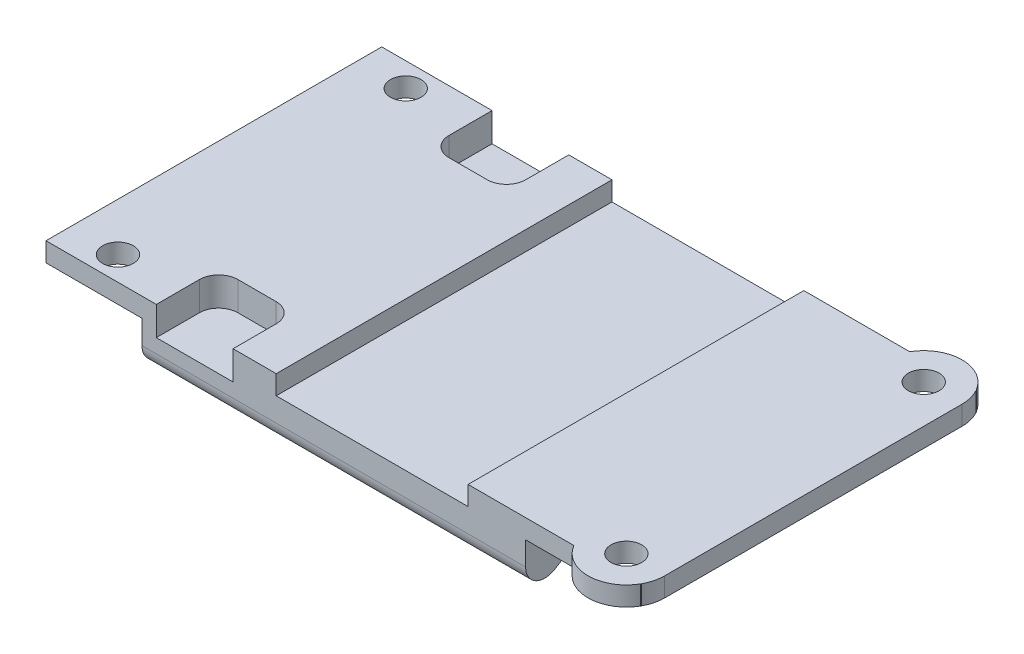
SolidWorks part; units mm, degrees
material "PEI"
ref_plane "Front Plane" through (0, 0, 0) normal (0, 0, 1) x (1, 0, 0)
ref_plane "Top Plane" through (0, 0, 0) normal (0, 1, 0) x (1, 0, 0)
ref_plane "Right Plane" through (0, 0, 0) normal (1, 0, 0) x (0, 0, -1)
sketch "Sketch1" plane through (0, 0, 0) normal (0, 1, 0) x (1, 0, 0)
  line L1 (20, -17.5) -> (-20, -17.5)
  line L2 (20, -17.5) -> (20, 17.5)
  line L3 (20, 17.5) -> (-20, 17.5)
  line L4 (-20, -17.5) -> (-20, 17.5)
  line L5 (20, -17.5) -> (-20, 17.5) construction
  line L6 (20, 17.5) -> (-20, -17.5) construction
  point P0 (0, 0)
  dimension "D1" = 35
  dimension "D2" = 40
extrude "Boss-Extrude1" add sketch "Sketch1" against normal blind 8
sketch "Sketch2" plane through (20, 0, 0) normal (1, 0, 0) x (0, 0, -1)
  line L0 (-17.5, -8) -> (-12.5, -5)
  line L1 (-12.5, -5) -> (12.5, -5)
  line L2 (0, -5) -> (0, -8)
  line L3 (17.5, -8) -> (12.5, -5)
  line L4 (17.5, 0) -> (-17.5, 0)
  line L5 (-17.5, 0) -> (-17.5, -8)
  line L6 (-17.5, -8) -> (17.5, -8)
  line L7 (17.5, -8) -> (17.5, 0)
  line L8 (17.5, 0) -> (-17.5, 0)
  line L9 (-17.5, 0) -> (-17.5, -8)
  line L10 (-17.5, -8) -> (17.5, -8)
  line L11 (17.5, -8) -> (17.5, 0)
  line M7 (-17.5, -8) -> (17.5, -8)
  dimension "D2" = 5
  dimension "D3" = 3
  dimension "D1" = 0
extrude "Cut-Extrude1" cut sketch "Sketch2" against normal through all and the other way through all contours L2 L1 L0 M7 | L3 L1 L2 M7 region at (20, -6.5833, 7.5694) region at (20, -6.5833, -7.5694)
fillet "Fillet1" radius 2 4 edges at (0, -5, 12.5) (0, -5, -12.5) (0, -8, -17.5) (0, -8, 17.5)
sketch "Sketch4" plane through (-20, 0, 0) normal (-1, 0, 0) x (0, 0, 1)
  line L1 (-17.5, 0) -> (17.5, 0)
  line L2 (-17.5, 0) -> (-17.5, -2)
  line L3 (-17.5, -2) -> (17.5, -2)
  line L4 (17.5, 0) -> (17.5, -2)
  line L6 (-17.5, 0) -> (-17.5, -4.4676)
  line L7 (-14.471, -6.1826) -> (-12.975, -5.285)
  line L8 (-11.946, -5) -> (11.946, -5)
  line L9 (12.975, -5.285) -> (14.471, -6.1826)
  line L10 (17.5, -4.4676) -> (17.5, 0)
  line L11 (17.5, 0) -> (-17.5, 0)
  line L12 (-17.5, 0) -> (-17.5, -4.4676)
  line L13 (-14.471, -6.1826) -> (-12.975, -5.285)
  line L14 (-11.946, -5) -> (11.946, -5)
  line L15 (12.975, -5.285) -> (14.471, -6.1826)
  line L16 (17.5, -4.4676) -> (17.5, 0)
  line L17 (17.5, 0) -> (-17.5, 0)
  arc A4 (-17.5, -4.4676) -> (-14.471, -6.1826) centre (-15.5, -4.4676) ccw
  arc A5 (-11.946, -5) -> (-12.975, -5.285) centre (-11.946, -7) ccw
  arc A6 (12.975, -5.285) -> (11.946, -5) centre (11.946, -7) ccw
  arc A7 (14.471, -6.1826) -> (17.5, -4.4676) centre (15.5, -4.4676) ccw
  arc A8 (-17.5, -4.4676) -> (-14.471, -6.1826) centre (-15.5, -4.4676) ccw
  arc A9 (-11.946, -5) -> (-12.975, -5.285) centre (-11.946, -7) ccw
  arc A10 (12.975, -5.285) -> (11.946, -5) centre (11.946, -7) ccw
  arc A11 (14.471, -6.1826) -> (17.5, -4.4676) centre (15.5, -4.4676) ccw
  line M12 (-17.5, 0) -> (-17.5, -4.4676)
  line M20 (17.5, -4.4676) -> (17.5, 0)
  line M21 (17.5, 0) -> (-17.5, 0)
  dimension "D2" = 2
  dimension "D1" = 0
extrude "Boss-Extrude2" add sketch "Sketch4" along normal blind 10 contours L3 M12 M20 M21 region at (-20, -1, 0)
sketch "Sketch5" plane through (20, 0, 0) normal (1, 0, 0) x (0, 0, -1)
  line L1 (-17.5, 0) -> (17.5, 0)
  line L2 (-17.5, 0) -> (-17.5, -2)
  line L3 (-17.5, -2) -> (17.5, -2)
  line L4 (17.5, 0) -> (17.5, -2)
  line L6 (12.975, -5.285) -> (14.471, -6.1826)
  line L7 (17.5, -4.4676) -> (17.5, 0)
  line L8 (17.5, 0) -> (-17.5, 0)
  line L9 (-17.5, 0) -> (-17.5, -4.4676)
  line L10 (-14.471, -6.1826) -> (-12.975, -5.285)
  line L11 (-11.946, -5) -> (11.946, -5)
  line L12 (12.975, -5.285) -> (14.471, -6.1826)
  line L13 (17.5, -4.4676) -> (17.5, 0)
  line L14 (17.5, 0) -> (-17.5, 0)
  line L15 (-17.5, 0) -> (-17.5, -4.4676)
  line L16 (-14.471, -6.1826) -> (-12.975, -5.285)
  line L17 (-11.946, -5) -> (11.946, -5)
  arc A4 (14.471, -6.1826) -> (17.5, -4.4676) centre (15.5, -4.4676) ccw
  arc A5 (-17.5, -4.4676) -> (-14.471, -6.1826) centre (-15.5, -4.4676) ccw
  arc A6 (-11.946, -5) -> (-12.975, -5.285) centre (-11.946, -7) ccw
  arc A7 (12.975, -5.285) -> (11.946, -5) centre (11.946, -7) ccw
  arc A8 (14.471, -6.1826) -> (17.5, -4.4676) centre (15.5, -4.4676) ccw
  arc A9 (-17.5, -4.4676) -> (-14.471, -6.1826) centre (-15.5, -4.4676) ccw
  arc A10 (-11.946, -5) -> (-12.975, -5.285) centre (-11.946, -7) ccw
  arc A11 (12.975, -5.285) -> (11.946, -5) centre (11.946, -7) ccw
  line M14 (17.5, -4.4676) -> (17.5, 0)
  line M15 (17.5, 0) -> (-17.5, 0)
  line M16 (-17.5, 0) -> (-17.5, -4.4676)
  dimension "D2" = 2
  dimension "D1" = 0
extrude "Boss-Extrude3" add sketch "Sketch5" along normal blind 12 contours L3 M16 M14 M15 region at (20, -1, 0)
sketch "Sketch6" plane through (0, -2, 0) normal (0, -1, 0) x (1, 0, 0)
  line L0 (0, 0) -> (-25, 0)
  line L1 (-25, 0) -> (-25, 15)
  line L4 (-20, -17.5) -> (-20, 17.5)
  line L5 (-20, 17.5) -> (-30, 17.5)
  line L6 (-30, 17.5) -> (-30, -17.5)
  line L7 (-30, -17.5) -> (-20, -17.5)
  line L8 (-20, -17.5) -> (-20, 17.5)
  line L9 (-20, 17.5) -> (-30, 17.5)
  line L10 (-30, 17.5) -> (-30, -17.5)
  line L11 (-30, -17.5) -> (-20, -17.5)
  line L12 (20, -11.946) -> (20, 11.946)
  line L13 (20, 11.946) -> (-20, 11.946)
  line L14 (-20, 11.946) -> (-20, -11.946)
  line L15 (-20, -11.946) -> (20, -11.946)
  line L16 (20, -11.946) -> (20, 11.946)
  line L17 (20, 11.946) -> (-20, 11.946)
  line L18 (-20, 11.946) -> (-20, -11.946)
  line L19 (-20, -11.946) -> (20, -11.946)
  circle A0 centre (-25, 15) radius 1.6
  circle A1 centre (-25, -15) radius 1.6
  dimension "D5" = 3.2
  dimension "D3" = 15
  dimension "D4" = 25
  dimension "D1" = 0
  dimension "D2" = 0
extrude "Cut-Extrude2" cut sketch "Sketch6" against normal blind 10 contours A1 | A0 region at (-26.0994, -2, 16.0994) region at (-25, -2, -15)
sketch "Sketch7" plane through (0, 0, 0) normal (0, 1, 0) x (1, 0, 0)
  line L0 (-25, -15) -> (-14.5, -15)
  line L1 (-14.5, -15) -> (-14.5, -14.5)
  line L2 (0, 0) -> (-16.7205, 0)
  line L3 (-10.5, -19) -> (-18.5, -19)
  line L4 (32, 17.5) -> (-30, 17.5)
  line L5 (-30, 17.5) -> (-30, -17.5)
  line L6 (-30, -17.5) -> (32, -17.5)
  line L7 (32, -17.5) -> (32, 17.5)
  line L8 (32, 17.5) -> (-30, 17.5)
  line L9 (-30, 17.5) -> (-30, -17.5)
  line L10 (-30, -17.5) -> (32, -17.5)
  line L11 (32, -17.5) -> (32, 17.5)
  line L12 (-10.5, -19) -> (-10.5, -11)
  line L13 (-10.5, -11) -> (-18.5, -11)
  line L14 (-18.5, -19) -> (-18.5, -11)
  line L15 (-10.5, -19) -> (-18.5, -11) construction
  line L16 (-10.5, -11) -> (-18.5, -19) construction
  line L17 (-10.5, 19) -> (-18.5, 19)
  line L18 (-18.5, 19) -> (-18.5, 11)
  line L19 (-10.5, 19) -> (-10.5, 11)
  line L20 (-10.5, 11) -> (-18.5, 11)
  dimension "D4" = 8
  dimension "D2" = 0.5
  dimension "D3" = 10.5
  dimension "D5" = 8
  dimension "D1" = 0
extrude "Cut-Extrude3" cut sketch "Sketch7" against normal blind 3 contours L20 L19 L8 L18 | L12 L13 L14 L3 region at (-14.5, 0, -14.25)
sketch "Sketch8" plane through (0, 0, 17.5) normal (0, 0, 1) x (1, 0, 0)
  line L0 (-10.5, 0) -> (32, 0) construction
  line L1 (14, 2) -> (-6, 2)
  line L2 (14, 2) -> (14, -2)
  line L3 (14, -2) -> (-6, -2)
  line L4 (-6, 2) -> (-6, -2)
  line L5 (14, 2) -> (-6, -2) construction
  line L6 (14, -2) -> (-6, 2) construction
  line L12 (-10.5, -3) -> (-18.5, -3)
  line L13 (-18.5, -3) -> (-18.5, 0)
  line L14 (-18.5, 0) -> (-30, 0)
  line L15 (-30, 0) -> (-30, -2)
  line L16 (-30, -2) -> (-20, -2)
  line L17 (-20, -2) -> (-20, -4.4676)
  line L18 (-20, -4.4676) -> (20, -4.4676)
  line L19 (20, -4.4676) -> (20, -2)
  line L20 (20, -2) -> (32, -2)
  line L21 (32, -2) -> (32, 0)
  line L22 (32, 0) -> (-10.5, 0)
  line L23 (-10.5, 0) -> (-10.5, -3)
  line L24 (-10.5, -3) -> (-18.5, -3)
  line L25 (-18.5, -3) -> (-18.5, 0)
  line L26 (-18.5, 0) -> (-30, 0)
  line L27 (-30, 0) -> (-30, -2)
  line L28 (-30, -2) -> (-20, -2)
  line L29 (-20, -2) -> (-20, -4.4676)
  line L30 (-20, -4.4676) -> (20, -4.4676)
  line L31 (20, -4.4676) -> (20, -2)
  line L32 (20, -2) -> (32, -2)
  line L33 (32, -2) -> (32, 0)
  line L34 (32, 0) -> (-10.5, 0)
  line L35 (-10.5, 0) -> (-10.5, -3)
  point P2 (4, 0)
  point P12 (0, 0)
  point P14 (0, 0)
  point P16 (0, 0)
  point P18 (2.753, 0)
  point P23 (-20, -3.2338)
  line M25 (32, 0) -> (-10.5, 0)
  dimension "D2" = 2
  dimension "D3" = 20
  dimension "D4" = 24
  dimension "D1" = 0
extrude "Cut-Extrude5" cut sketch "Sketch8" against normal through all contours L4 L3 L2 M25 region at (4, -1, 17.5)
fillet "Fillet2" radius 2 4 edges at (-18.5, -1.5, 11) (-10.5, -1.5, 11) (-18.5, -1.5, -11) (-10.5, -1.5, -11)
sketch "Sketch10" plane through (0, -2, 0) normal (0, -1, 0) x (1, 0, 0)
  line L0 (-25, 15) -> (28.5, 15)
  line L1 (0, 0) -> (0, 15.5)
  line L2 (0, 15.5) -> (28.5, 15.5)
  line L3 (28.5, 15.5) -> (28.5, 15)
  line L4 (20, 17.5) -> (20, -17.5)
  line L5 (20, -17.5) -> (32, -17.5)
  line L6 (32, -17.5) -> (32, 17.5)
  line L7 (32, 17.5) -> (20, 17.5)
  line L8 (20, 17.5) -> (20, -17.5)
  line L9 (20, -17.5) -> (32, -17.5)
  line L10 (32, -17.5) -> (32, 17.5)
  line L11 (32, 17.5) -> (20, 17.5)
  line L12 (-20, -17.5) -> (-20, 17.5)
  line L13 (-20, 17.5) -> (-30, 17.5)
  line L14 (-30, 17.5) -> (-30, -17.5)
  line L15 (-30, -17.5) -> (-20, -17.5)
  line L16 (-20, -17.5) -> (-20, 17.5)
  line L17 (-20, 17.5) -> (-30, 17.5)
  line L18 (-30, 17.5) -> (-30, -17.5)
  line L19 (-30, -17.5) -> (-20, -17.5)
  line L20 (0, 0) -> (12.4483, 0)
  line L21 (32.5, 15.5) -> (32.5, -15.5)
  circle A2 centre (28.5, 15.5) radius 1.6
  circle A3 centre (28.5, 15.5) radius 4
  circle A4 centre (28.5, -15.5) radius 1.6
  circle A5 centre (28.5, -15.5) radius 4
  line M13 (32, -17.5) -> (32, 17.5)
  dimension "D4" = 3.2
  dimension "D6" = 8
  dimension "D3" = 53.5
  dimension "D5" = 15.5
  dimension "D1" = 0
  dimension "D2" = 0
extrude "Cut-Extrude6" cut sketch "Sketch10" against normal through all contours A4 | A2 region at (28.5, -2, -15.5)
extrude "Boss-Extrude4" add sketch "Sketch10<4>" against normal blind 2 contours L11 A3 | L10 A3 | A5 L9 | A5 L10 | A5 L21 A3 M13 region at (32.2545, -2, 0) region at (32.2011, -2, 15.5) region at (28.5, -2, -18.3201) region at (28.5, -2, 18.3201) region at (32.2011, -2, -15.5)
sketch "Sketch10<4>" plane through (0, -2, 0) normal (0, -1, 0) x (1, 0, 0) same geometry as "Sketch10"
